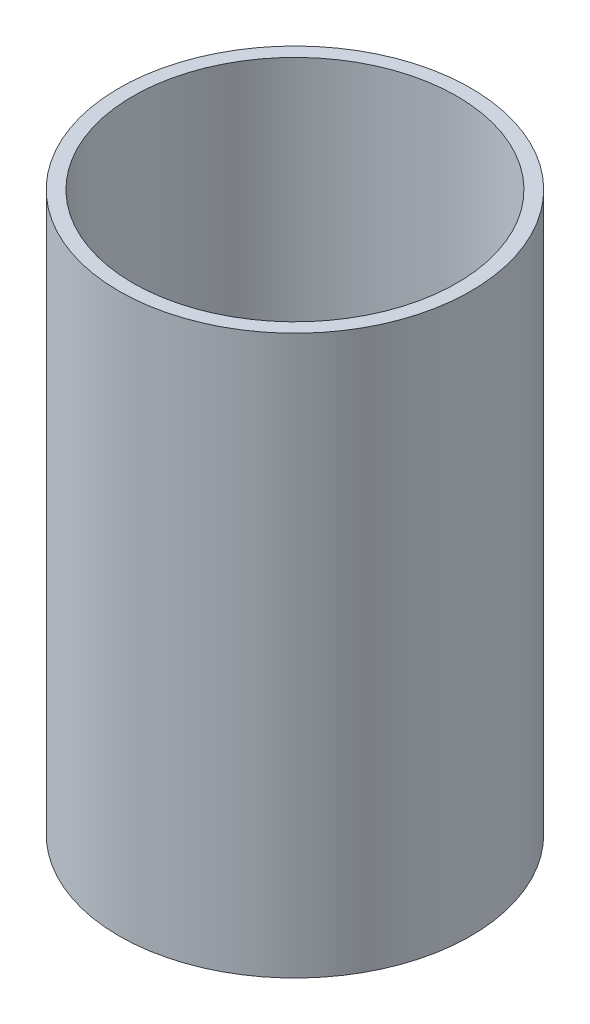
SolidWorks part; units mm, degrees
ref_plane "Plan de face" through (0, 0, 0) normal (0, 0, 1) x (1, 0, 0)
ref_plane "Plan de dessus" through (0, 0, 0) normal (0, 1, 0) x (1, 0, 0)
ref_plane "Plan de droite" through (0, 0, 0) normal (1, 0, 0) x (0, 0, -1)
sketch "Esquisse1" plane through (0, 0, 0) normal (0, 1, 0) x (1, 0, 0)
  circle A0 centre (0, 0) radius 31.5
  circle A1 centre (0, 0) radius 29
  dimension "D1" = 63
  dimension "D2" = 58
extrude "Boss.-Extru.1" add sketch "Esquisse1" along normal blind 100
